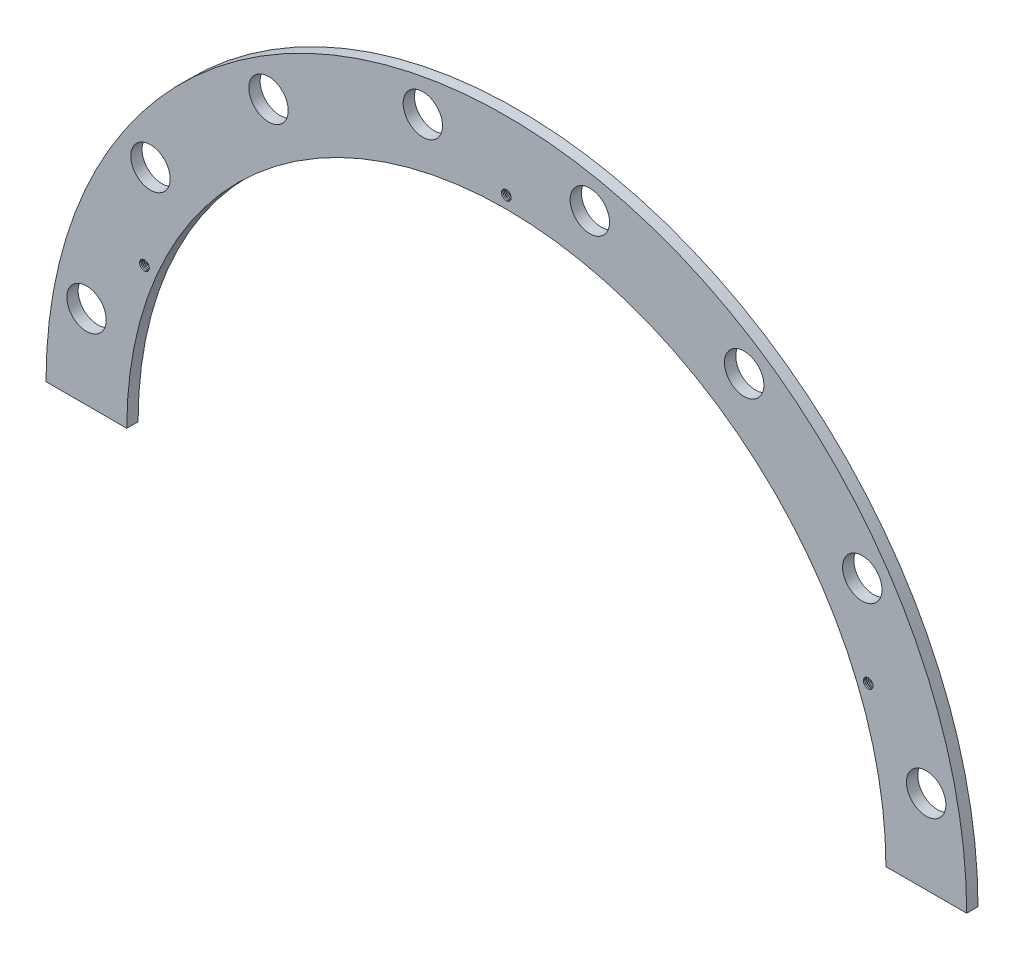
SolidWorks part; units mm, degrees
ref_plane "Piano frontale" through (0, 0, 0) normal (0, 0, 1) x (1, 0, 0)
ref_plane "Piano superiore" through (0, 0, 0) normal (0, 1, 0) x (1, 0, 0)
ref_plane "Piano destro" through (0, 0, 0) normal (1, 0, 0) x (0, 0, -1)
sketch "Schizzo1" plane through (0, 0, 0) normal (0, 0, 1) x (1, 0, 0)
  line L0 (-285, 0) -> (-235, 0)
  line L1 (235, 0) -> (285, 0)
  arc A0 (235, 0) -> (-235, 0) centre (0, 0) ccw
  arc A1 (285, 0) -> (-285, 0) centre (0, 0) ccw
  dimension "D1" = 470
  dimension "D2" = 570
extrude "Estrusione-Estrusione1" add sketch "Schizzo1" along normal blind 7
sketch "Schizzo2" plane through (0, 0, 7) normal (0, 0, 1) x (1, 0, 0)
  line L0 (-259.9081, 51.6989) -> (0, 0) construction
  line L1 (0, 0) -> (-265, 0) construction
  circle A0 centre (0, 0) radius 265 construction
  circle A1 centre (-259.9081, 51.6989) radius 12.2
  dimension "D1" = 530
  dimension "D2" = 24.4
  dimension "D3" = 11.25
extrude "Taglio-Estrusione1" cut sketch "Schizzo2" along direction (0, 0, 1) on the side against the normal through all
pattern_circular "RipetizioneCircolare1" count 8 every 22.5 about axis through (0, 0, 0) along (0, 0, -1) of "Taglio-Estrusione1"
sketch "Schizzo3" plane through (0, 0, 7) normal (0, 0, 1) x (1, 0, 0)
  line L0 (-224.0408, 92.8007) -> (0, 0) construction
  line L1 (0, 0) -> (-260, 0) construction
  line L2 (-285, 0) -> (-235, 0) construction
  circle A0 centre (0, 0) radius 242.5 construction
  circle A1 centre (-224.0408, 92.8007) radius 3
  dimension "D1" = 485
  dimension "D2" = 6
  dimension "D3" = 22.5
extrude "Taglio-Estrusione2" cut sketch "Schizzo3" along direction (0, 0, 1) on the side against the normal through all
pattern_circular "RipetizioneCircolare2" count 3 every 67.5 about axis through (0, 0, 7) along (0, 0, -1) of "Taglio-Estrusione2"
thread "Filettatura1" pitch 1 method cut profile "Profilo filettatura1" start angle 0, offset 0, length 0, pitch 1, diameter 6
ref_plane "Piano1" through (-3, 242.5, 7) normal (0, -1, 0) x (-1, 0, 0)
sketch "Profilo filettatura1" plane through (-3, 242.5, 7) normal (0, -1, 0) x (-1, 0, 0)
  line L0 (0, 0) -> (0, 1) construction
  line L1 (0, 0) -> (0.5413, 0.3125)
  line L2 (0.5413, 0.3125) -> (0.5413, 0.4375)
  line L3 (0.5413, 0.4375) -> (0, 0.75)
  line L4 (0.5413, 0.375) -> (0, 0.375) construction
  line L11 (0, 0) -> (0, 0.75)
  point P2 (0, 0)
  dimension "Pitch" = 1
  dimension "Profile_Angle" = 60
  dimension "Profile_Land" = 0.125
  dimension "Profile_Height" = 0.5413
thread "Filettatura2" pitch 1 method cut profile "Profilo filettatura2" start angle 0, offset 0, length 0, pitch 1, diameter 6
ref_plane "Piano2" through (-227.0408, 92.8007, 7) normal (0, -1, 0) x (-1, 0, 0)
sketch "Profilo filettatura2" plane through (-227.0408, 92.8007, 7) normal (0, -1, 0) x (-1, 0, 0)
  line L0 (0, 0) -> (0, 1) construction
  line L1 (0, 0) -> (0.5413, 0.3125)
  line L2 (0.5413, 0.3125) -> (0.5413, 0.4375)
  line L3 (0.5413, 0.4375) -> (0, 0.75)
  line L4 (0.5413, 0.375) -> (0, 0.375) construction
  line L11 (0, 0) -> (0, 0.75)
  point P2 (0, 0)
  dimension "Pitch" = 1
  dimension "Profile_Angle" = 60
  dimension "Profile_Land" = 0.125
  dimension "Profile_Height" = 0.5413
thread "Filettatura3" pitch 1 method cut profile "Profilo filettatura3" start angle 0, offset 0, length 0, pitch 1, diameter 6
ref_plane "Piano3" through (221.0408, 92.8007, 7) normal (0, -1, 0) x (-1, 0, 0)
sketch "Profilo filettatura3" plane through (221.0408, 92.8007, 7) normal (0, -1, 0) x (-1, 0, 0)
  line L0 (0, 0) -> (0, 1) construction
  line L1 (0, 0) -> (0.5413, 0.3125)
  line L2 (0.5413, 0.3125) -> (0.5413, 0.4375)
  line L3 (0.5413, 0.4375) -> (0, 0.75)
  line L4 (0.5413, 0.375) -> (0, 0.375) construction
  line L11 (0, 0) -> (0, 0.75)
  point P2 (0, 0)
  dimension "Pitch" = 1
  dimension "Profile_Angle" = 60
  dimension "Profile_Land" = 0.125
  dimension "Profile_Height" = 0.5413
